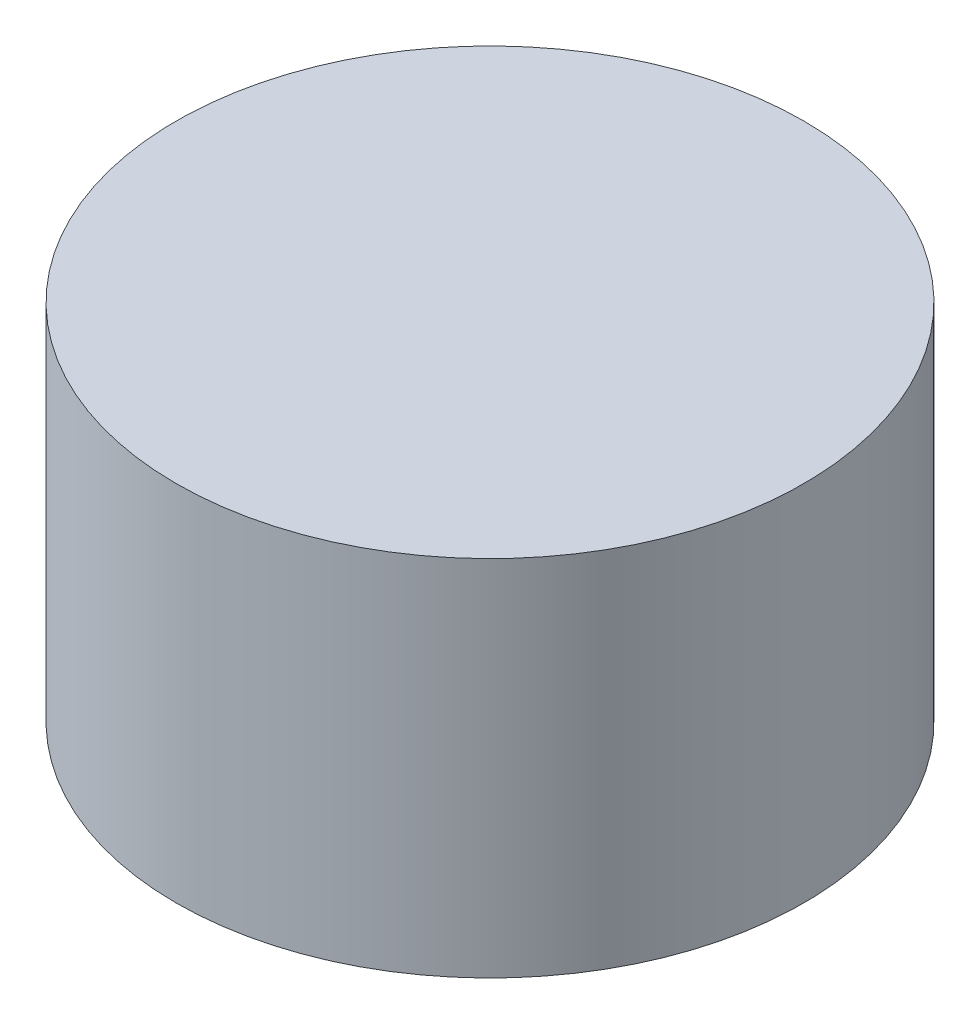
SolidWorks part; units mm, degrees
ref_plane "Front Plane" through (0, 0, 0) normal (0, 0, 1) x (1, 0, 0)
ref_plane "Top Plane" through (0, 0, 0) normal (0, 1, 0) x (1, 0, 0)
ref_plane "Right Plane" through (0, 0, 0) normal (1, 0, 0) x (0, 0, -1)
sketch "Sketch1" plane through (0, 0, 0) normal (0, 1, 0) x (1, 0, 0)
  circle A0 centre (0, 0) radius 60.5
extrude "Boss-Extrude1" add sketch "Sketch1" along normal blind 70
sketch "Sketch2" plane through (0, 0, 0) normal (1, 0, 0) x (0, 0, -1)
  line L0 (0, 0) -> (0, 63.4235) construction
ref_axis "Axis1" through (0, 0, 0) along (0, 1, 0)
